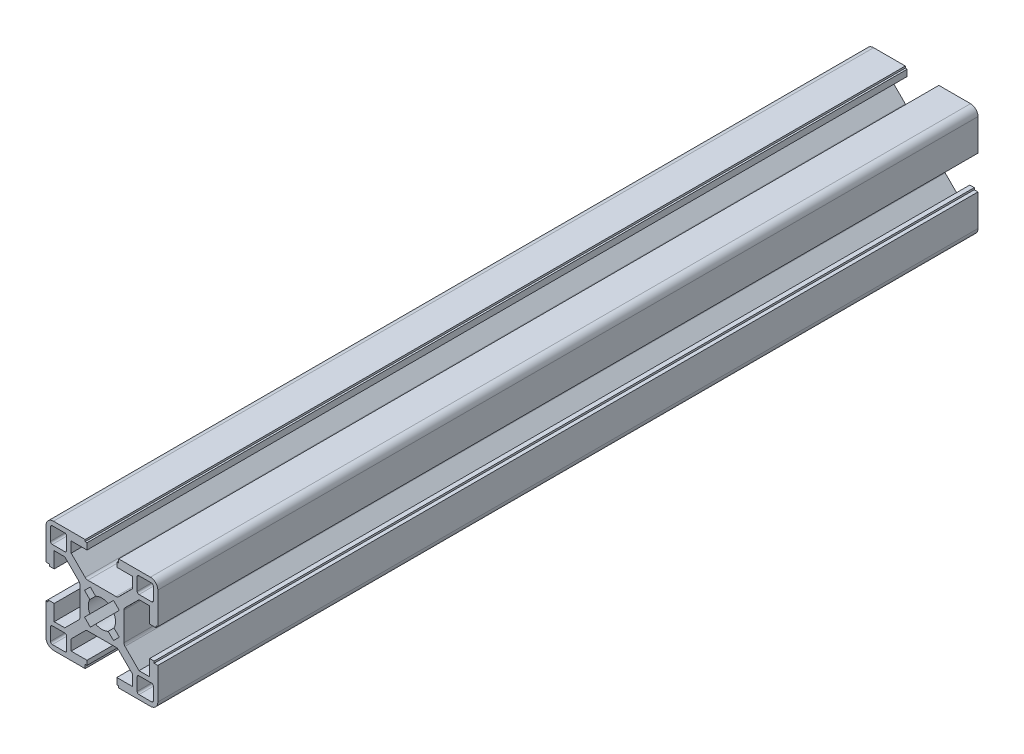
SolidWorks part; units mm, degrees
material "6061-T6 (SS)"
ref_plane "Front Plane" through (0, 0, 0) normal (0, 0, 1) x (1, 0, 0)
ref_plane "Top Plane" through (0, 0, 0) normal (0, 1, 0) x (1, 0, 0)
ref_plane "Right Plane" through (0, 0, 0) normal (1, 0, 0) x (0, 0, -1)
sketch "Sketch1" plane through (0, 0, 0) normal (0, 0, 1) x (1, 0, 0)
  line L0 (-4.5, 15) -> (-4.5, 14.5)
  line L1 (13, -15) -> (4.5, -15)
  line L2 (15, -13) -> (15, -4.5)
  line L3 (13, 15) -> (4.5, 15)
  line L4 (-15, -13) -> (-15, -4.5)
  line L5 (15, -15) -> (-15, 15) construction
  line L6 (15, 15) -> (-15, -15) construction
  line L7 (-4.5, 14.5) -> (-4, 14.5)
  line L8 (-4, 14.5) -> (-4, 12.8)
  line L9 (-4, 12.8) -> (-8.25, 12.8)
  line L10 (-8.25, 12.8) -> (-8.25, 9.95)
  line L11 (-8.25, 9.95) -> (-4.4929, 6.1929)
  line L12 (-3.7858, 5.9) -> (3.7858, 5.9)
  line L13 (4.4929, 6.1929) -> (8.25, 9.95)
  line L14 (8.25, 9.95) -> (8.25, 12.8)
  line L15 (8.25, 12.8) -> (4, 12.8)
  line L16 (4, 12.8) -> (4, 14)
  line L17 (4, 14) -> (4.5, 14)
  line L18 (4.5, 14) -> (4.5, 15)
  line L19 (0, 0) -> (0, 16.8698) construction
  line L20 (-4.5, 15) -> (-13, 15)
  line L21 (12.8, 8.25) -> (9.95, 8.25)
  line L22 (9.95, 8.25) -> (6.1929, 4.4929)
  line L23 (5.9, 3.7858) -> (5.9, -3.7858)
  line L24 (6.1929, -4.4929) -> (9.95, -8.25)
  line L25 (9.95, -8.25) -> (12.8, -8.25)
  line L26 (12.8, -8.25) -> (12.8, -4)
  line L27 (12.8, 4) -> (12.8, 8.25)
  line L28 (12.8, -4) -> (14, -4)
  line L29 (14, -4) -> (14, -4.5)
  line L30 (14, -4.5) -> (15, -4.5)
  line L31 (14.5, 4) -> (12.8, 4)
  line L32 (14.5, 4.5) -> (14.5, 4)
  line L33 (15, 4.5) -> (14.5, 4.5)
  line L34 (8.25, -12.8) -> (8.25, -9.95)
  line L35 (8.25, -9.95) -> (4.4929, -6.1929)
  line L36 (3.7858, -5.9) -> (-3.7858, -5.9)
  line L37 (-4.4929, -6.1929) -> (-8.25, -9.95)
  line L38 (-8.25, -9.95) -> (-8.25, -12.8)
  line L39 (-8.25, -12.8) -> (-4, -12.8)
  line L40 (4, -12.8) -> (8.25, -12.8)
  line L41 (-4, -12.8) -> (-4, -14)
  line L42 (-4, -14) -> (-4.5, -14)
  line L43 (-4.5, -14) -> (-4.5, -15)
  line L44 (4, -14.5) -> (4, -12.8)
  line L45 (4.5, -14.5) -> (4, -14.5)
  line L46 (4.5, -15) -> (4.5, -14.5)
  line L47 (-12.8, -8.25) -> (-9.95, -8.25)
  line L48 (-9.95, -8.25) -> (-6.1929, -4.4929)
  line L49 (-5.9, -3.7858) -> (-5.9, 3.7858)
  line L50 (-6.1929, 4.4929) -> (-9.95, 8.25)
  line L51 (-9.95, 8.25) -> (-12.8, 8.25)
  line L52 (-12.8, 8.25) -> (-12.8, 4)
  line L53 (-12.8, -4) -> (-12.8, -8.25)
  line L54 (-12.8, 4) -> (-14, 4)
  line L55 (-14, 4) -> (-14, 4.5)
  line L56 (-14, 4.5) -> (-15, 4.5)
  line L57 (-14.5, -4) -> (-12.8, -4)
  line L58 (-14.5, -4.5) -> (-14.5, -4)
  line L59 (-15, -4.5) -> (-14.5, -4.5)
  line L60 (15, 4.5) -> (15, 13)
  line L61 (-15, 4.5) -> (-15, 13)
  line L62 (-4.5, -15) -> (-13, -15)
  line L63 (13.3, -9.45) -> (9.95, -9.45)
  line L64 (9.95, 13.8) -> (13.3, 13.8)
  line L65 (9.45, 13.3) -> (9.45, 9.95)
  line L66 (9.95, 9.45) -> (13.3, 9.45)
  line L67 (13.8, 13.3) -> (13.8, 9.95)
  line L68 (13.8, -9.95) -> (13.8, -13.3)
  line L69 (13.3, -13.8) -> (9.95, -13.8)
  line L70 (9.45, -9.95) -> (9.45, -13.3)
  line L71 (-9.45, -13.3) -> (-9.45, -9.95)
  line L72 (-9.95, -13.8) -> (-13.3, -13.8)
  line L73 (-13.8, -13.3) -> (-13.8, -9.95)
  line L74 (-9.95, -9.45) -> (-13.3, -9.45)
  line L75 (-13.3, 9.45) -> (-9.95, 9.45)
  line L76 (-13.8, 9.95) -> (-13.8, 13.3)
  line L77 (-13.3, 13.8) -> (-9.95, 13.8)
  line L78 (-9.45, 9.95) -> (-9.45, 13.3)
  line L79 (-1.6831, -3.2388) -> (-3.1113, -4.6669)
  line L80 (3.1113, 4.6669) -> (4.6669, 3.1113)
  line L81 (4.6669, 3.1113) -> (3.2388, 1.6831)
  line L82 (-3.1113, -4.6669) -> (-4.6669, -3.1113)
  line L83 (-4.6669, -3.1113) -> (-3.2388, -1.6831)
  line L85 (3.1113, -4.6669) -> (4.6669, -3.1113)
  line L86 (3.1113, -4.6669) -> (1.6831, -3.2388)
  line L87 (-4.6669, 3.1113) -> (-3.1113, 4.6669)
  line L88 (-3.1113, 4.6669) -> (-1.6831, 3.2388)
  line L93 (3.2388, -1.6831) -> (4.6669, -3.1113)
  line L95 (1.6831, 3.2388) -> (3.1113, 4.6669)
  line L98 (-3.2388, 1.6831) -> (-4.6669, 3.1113)
  arc A0 (-3.2388, 1.6831) -> (-3.2388, -1.6831) centre (0, 0) ccw
  arc A1 (13, 15) -> (15, 13) centre (13, 13) cw
  arc A2 (15, -13) -> (13, -15) centre (13, -13) cw
  arc A3 (-13, -15) -> (-15, -13) centre (-13, -13) cw
  arc A4 (-15, 13) -> (-13, 15) centre (-13, 13) cw
  arc A5 (-6.1929, 4.4929) -> (-5.9, 3.7858) centre (-6.9, 3.7858) cw
  arc A6 (9.95, 13.8) -> (9.45, 13.3) centre (9.95, 13.3) ccw
  arc A7 (-5.9, -3.7858) -> (-6.1929, -4.4929) centre (-6.9, -3.7858) cw
  arc A8 (-4.4929, -6.1929) -> (-3.7858, -5.9) centre (-3.7858, -6.9) cw
  arc A9 (9.45, 9.95) -> (9.95, 9.45) centre (9.95, 9.95) ccw
  arc A10 (13.8, 9.95) -> (13.3, 9.45) centre (13.3, 9.95) cw
  arc A11 (13.8, 13.3) -> (13.3, 13.8) centre (13.3, 13.3) ccw
  arc A12 (13.8, -9.95) -> (13.3, -9.45) centre (13.3, -9.95) ccw
  arc A13 (13.3, -13.8) -> (13.8, -13.3) centre (13.3, -13.3) ccw
  arc A14 (9.95, -13.8) -> (9.45, -13.3) centre (9.95, -13.3) cw
  arc A15 (9.95, -9.45) -> (9.45, -9.95) centre (9.95, -9.95) ccw
  arc A16 (1.6831, 3.2388) -> (-1.6831, 3.2388) centre (0, 0) ccw
  arc A17 (-9.95, -13.8) -> (-9.45, -13.3) centre (-9.95, -13.3) ccw
  arc A18 (-13.8, -13.3) -> (-13.3, -13.8) centre (-13.3, -13.3) ccw
  arc A19 (-13.8, -9.95) -> (-13.3, -9.45) centre (-13.3, -9.95) cw
  arc A20 (-9.45, -9.95) -> (-9.95, -9.45) centre (-9.95, -9.95) ccw
  arc A21 (1.6831, 3.2388) -> (-1.6831, 3.2388) centre (0, 0) ccw
  arc A22 (-13.8, 9.95) -> (-13.3, 9.45) centre (-13.3, 9.95) ccw
  arc A23 (-13.3, 13.8) -> (-13.8, 13.3) centre (-13.3, 13.3) ccw
  arc A24 (-9.95, 13.8) -> (-9.45, 13.3) centre (-9.95, 13.3) cw
  arc A25 (-9.95, 9.45) -> (-9.45, 9.95) centre (-9.95, 9.95) ccw
  arc A26 (3.2388, -1.6831) -> (3.2388, 1.6831) centre (0, 0) ccw
  arc A27 (3.7858, -5.9) -> (4.4929, -6.1929) centre (3.7858, -6.9) cw
  arc A28 (6.1929, -4.4929) -> (5.9, -3.7858) centre (6.9, -3.7858) cw
  arc A29 (5.9, 3.7858) -> (6.1929, 4.4929) centre (6.9, 3.7858) cw
  arc A30 (4.4929, 6.1929) -> (3.7858, 5.9) centre (3.7858, 6.9) cw
  arc A31 (-3.7858, 5.9) -> (-4.4929, 6.1929) centre (-3.7858, 6.9) cw
  arc A32 (3.2388, -1.6831) -> (3.2388, 1.6831) centre (0, 0) ccw
  arc A33 (-3.2388, 1.6831) -> (-3.2388, -1.6831) centre (0, 0) ccw
  arc A34 (-1.6831, -3.2388) -> (1.6831, -3.2388) centre (0, 0) ccw
  arc A35 (-1.6831, -3.2388) -> (1.6831, -3.2388) centre (0, 0) ccw
  point P0 (0, 0)
  point P70 (0, 0)
  point P135 (0, 0)
  point P144 (4.2, 5.9)
  point P147 (-4.2, 5.9)
  point P151 (0, 0)
  point P154 (3.8891, 3.8891)
  point P159 (0, 0)
  point P162 (3.8891, -3.8891)
  dimension "D18" = 7.3
  dimension "D20" = 2
  dimension "D21" = 1
  dimension "D22" = 1.2
  dimension "D23" = 30
  dimension "D28" = 0.5
  dimension "D1" = 30
  dimension "D2" = 30
  dimension "D3" = 8
  dimension "D4" = 4
  dimension "D5" = 9
  dimension "D6" = 4.5
  dimension "D7" = 1
  dimension "D8" = 0.5
  dimension "D9" = 16.5
  dimension "D10" = 8.25
  dimension "D11" = 2.2
  dimension "D12" = 2.2
  dimension "D13" = 9.1
  dimension "D14" = 2.4042
  dimension "D16" = 45
  dimension "D17" = 45
  dimension "D25" = 1.2
  dimension "D26" = 1.2
  dimension "D27" = 1.2
  dimension "D19" = 4
extrude "Boss-Extrude1" add sketch "Sketch1" along normal blind 220 contours A0 | L75 A25 L78 A24 L77 A23 L76 A22 | L71 A20 L74 A19 L73 A18 L72 A17 | L63 A15 L70 A14 L69 A13 L68 A12 | L67 A11 L64 A6 L65 A9 L66 A10 | L36 A8 L37 L38 L39 L41 L42 L43 L62 A3 L4 L59 L58 L57 L53 L47 L48 A7 L49 A5 L50 L51 L52 L54 L55 L56 L61 A4 L20 L0 L7 L8 L9 L10 L11 A31 L12 A30 L13 L14 L15 L16 L17 L18 L3 A1 L60 L33 L32 L31 L27 L21 L22 A29 L23 A28 L24 L25 L26 L28 L29 L30 L2 A2 L1 L46 L45 L44 L40 L34 L35 A27 region at (11.625, -11.625, 0) region at (11.625, 11.625, 0) region at (-11.625, -11.625, 0) region at (-11.625, 11.625, 0) region at (0, 0, 0)
